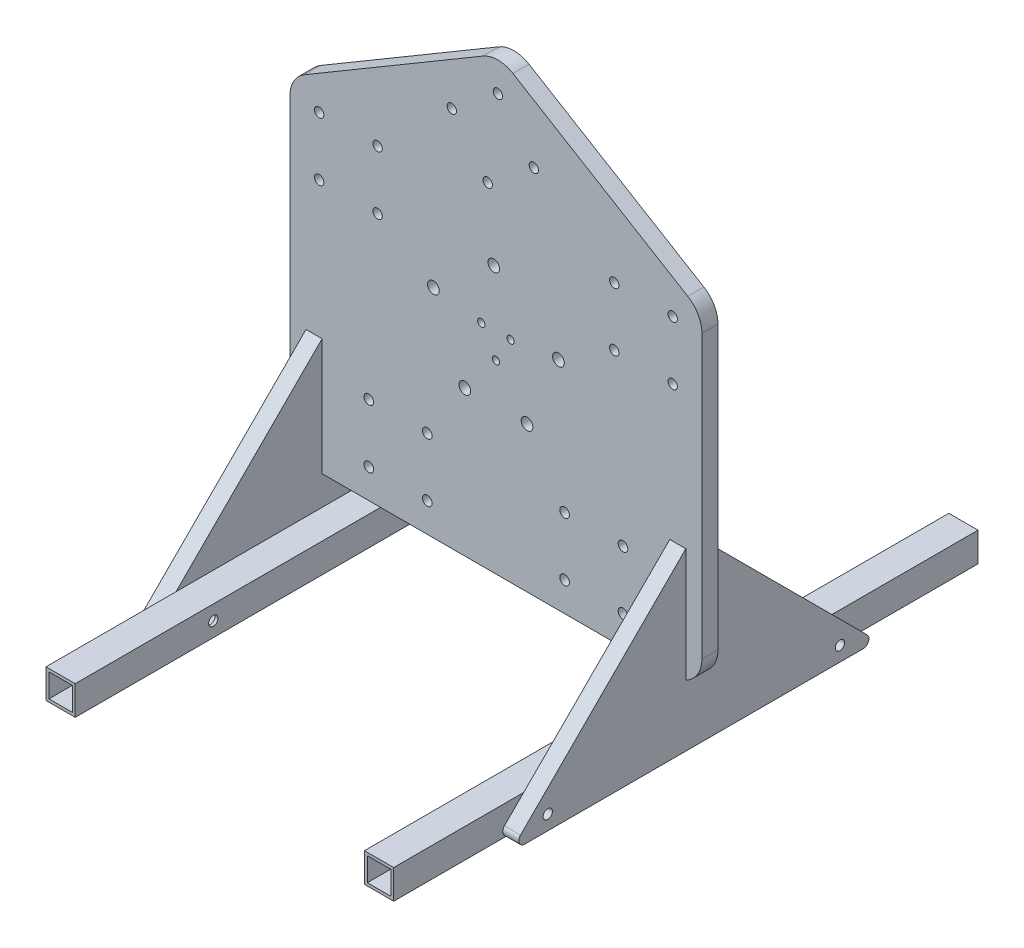
SolidWorks part; units mm, degrees
material "ﾊﾞﾙｻ"
ref_plane "正面" through (0, 0, 0) normal (0, 0, 1) x (1, 0, 0)
ref_plane "平面" through (0, 0, 0) normal (0, 1, 0) x (1, 0, 0)
ref_plane "右側面" through (0, 0, 0) normal (1, 0, 0) x (0, 0, -1)
sketch "ｽｹｯﾁ2" plane through (0, 0, 0) normal (0, 0, 1) x (1, 0, 0)
  line L0 (0, 0) -> (0, -57) construction
  line L5 (-23.5, -27) -> (-43.5, -27) construction
  line L6 (-23.5, -27) -> (-23.5, -47) construction
  line L7 (-23.5, -47) -> (-43.5, -47) construction
  line L8 (-43.5, -27) -> (-43.5, -47) construction
  line L9 (43.5, -27) -> (43.5, -47) construction
  line L10 (23.5, -47) -> (43.5, -47) construction
  line L11 (23.5, -27) -> (23.5, -47) construction
  line L12 (23.5, -27) -> (43.5, -27) construction
  line L13 (-23.5, -27) -> (-6, 0) construction
  line L14 (-40.5, 29.5934) -> (-13.5, 12.0934) construction
  line L15 (40.5, 49.5934) -> (40.5, 29.5934) construction
  line L16 (-60.5, 49.5934) -> (-40.5, 49.5934) construction
  line L17 (-60.5, 49.5934) -> (-60.5, 29.5934) construction
  line L18 (-60.5, 29.5934) -> (-40.5, 29.5934) construction
  line L19 (-40.5, 49.5934) -> (-40.5, 29.5934) construction
  line L20 (60.5, 29.5934) -> (40.5, 29.5934) construction
  line L21 (60.5, 49.5934) -> (60.5, 29.5934) construction
  line L22 (60.5, 49.5934) -> (40.5, 49.5934) construction
  line L23 (40.5, 29.5934) -> (13.5, 12.0934) construction
  line L24 (-2.8043, 57.6463) -> (0, 25.5934) construction
  line L25 (0.6676, 85.7166) -> (12.9669, 69.9455) construction
  line L26 (0.6676, 85.7166) -> (-15.1035, 73.4174) construction
  line L27 (-15.1035, 73.4174) -> (-2.8043, 57.6463) construction
  line L28 (12.9669, 69.9455) -> (-2.8043, 57.6463) construction
  line L29 (23.5, -27) -> (6, 0) construction
  line L30 (-70.5, 49.5934) -> (-70.5, -47)
  line L31 (-60.5, -57) -> (60.5, -57)
  line L32 (70.5, -47) -> (70.5, 49.5934)
  line L33 (65.6685, 58.1542) -> (5.8361, 94.2774)
  line L34 (-4.4175, 94.3272) -> (-65.5851, 58.204)
  line L35 (0, 12.0934) -> (0, 6.3199) construction
  circle A0 centre (-43.5, -47) radius 1.65
  circle A1 centre (-43.5, -27) radius 1.65
  circle A2 centre (-23.5, -27) radius 1.65
  circle A3 centre (-23.5, -47) radius 1.65
  circle A8 centre (23.5, -47) radius 1.65
  circle A9 centre (23.5, -27) radius 1.65
  circle A10 centre (43.5, -27) radius 1.65
  circle A11 centre (43.5, -47) radius 1.65
  circle A12 centre (-60.5, 49.5934) radius 1.6
  circle A13 centre (-60.5, 29.5934) radius 1.6
  circle A14 centre (-40.5, 29.5934) radius 1.6
  circle A15 centre (-40.5, 49.5934) radius 1.6
  circle A16 centre (40.5, 49.5934) radius 1.6
  circle A17 centre (40.5, 29.5934) radius 1.6
  circle A18 centre (60.5, 29.5934) radius 1.6
  circle A19 centre (60.5, 49.5934) radius 1.6
  circle A20 centre (0.6676, 85.7166) radius 1.6
  circle A21 centre (-15.1035, 73.4174) radius 1.6
  circle A22 centre (-2.8043, 57.6463) radius 1.6
  circle A23 centre (12.9669, 69.9455) radius 1.6
  circle A24 centre (0, 12.0934) radius 13.5 construction
  arc A25 (-70.5, -47) -> (-60.5, -57) centre (-60.5, -47) ccw
  arc A26 (60.5, -57) -> (70.5, -47) centre (60.5, -47) ccw
  arc A27 (70.5, 49.5934) -> (65.6685, 58.1542) centre (60.5, 49.5934) ccw
  arc A28 (5.8361, 94.2774) -> (-4.4175, 94.3272) centre (0.6676, 85.7166) ccw
  arc A29 (-70.5, 49.5934) -> (-65.5851, 58.204) centre (-60.5, 49.5934) cw
  circle A30 centre (0, 12.0934) radius 22 construction
  circle A31 centre (-21.3964, 17.2114) radius 2
  circle A32 centre (-0.7426, 34.0809) radius 2
  circle A33 centre (21.3964, 17.2114) radius 2
  circle A34 centre (10.6418, -7.1616) radius 2
  circle A35 centre (-10.6418, -7.1616) radius 2
  circle A36 centre (0, 6.3199) radius 1.25
  circle A37 centre (-5, 14.9801) radius 1.25
  circle A38 centre (5, 14.9801) radius 1.25
  point P83 (0, 12.0934)
  dimension "D5" = 3.3
  dimension "D9" = 3.2
  dimension "D13" = 27
  dimension "D14" = 10
  dimension "D17" = 4
  dimension "D18" = 2.5
  dimension "D1" = 20
  dimension "D2" = 17.5
  dimension "D4" = 20
  dimension "D6" = 6
  dimension "24.5" = 27
  dimension "D7" = 20
  dimension "D8" = 20
  dimension "D10" = 17.5
  dimension "D11" = 27
  dimension "D15" = 185
  dimension "6" = 8.5
  dimension "D20" = 10
  dimension "D12" = 2
  dimension "D19" = 3
extrude "ﾎﾞｽ - 押し出し1" add sketch "ｽｹｯﾁ2" along normal blind 5.5
sketch "ｽｹｯﾁ4" plane through (0, 0, 0) normal (0, 0, -1) x (-1, 0, 0)
  circle A0 centre (0.7426, 34.0809) radius 1.7
  circle A1 centre (-21.3964, 17.2114) radius 1.7
  circle A2 centre (21.3964, 17.2114) radius 1.7
  circle A3 centre (10.6418, -7.1616) radius 1.7
  circle A4 centre (-10.6418, -7.1616) radius 1.7
  circle A6 centre (0, 12.0934) radius 22 construction
  circle A7 centre (0, 12.0934) radius 27
  circle A8 centre (0, 6.3199) radius 1.6
  circle A9 centre (0, 6.3199) radius 1.25 construction
  circle A10 centre (-5, 14.9801) radius 1.6
  circle A11 centre (5, 14.9801) radius 1.6
  dimension "D1" = 3.4
  dimension "D2" = 5
  dimension "D3" = 3.2
extrude "ﾎﾞｽ - 押し出し2" add sketch "ｽｹｯﾁ4" along normal blind 10 separate body
sketch "ｽｹｯﾁ6" plane through (0, 0, 5.5) normal (0, 0, 1) x (1, 0, 0)
  line L0 (0, 0) -> (0, -57) construction
  line L1 (-60.5, -57) -> (60.5, -57) construction
  line L2 (70.5, -47) -> (70.5, 49.5934) construction
  line L3 (59.5, -37) -> (65, -37)
  line L4 (59.5, -37) -> (59.5, -57)
  line L5 (59.5, -57) -> (65, -57)
  line L6 (65, -37) -> (65, -57)
  line L7 (-59.5, -57) -> (-65, -57)
  line L8 (-65, -37) -> (-65, -57)
  line L9 (-59.5, -37) -> (-65, -37)
  line L10 (-59.5, -37) -> (-59.5, -57)
  dimension "D1" = 5.5
  dimension "D2" = 5.5
  dimension "D3" = 20
extrude "ｶｯﾄ - 押し出し1" cut sketch "ｽｹｯﾁ6" against normal through all
sketch "ｽｹｯﾁ7" plane through (65, 0, 0) normal (-1, 0, 0) x (0, 0, 1)
  line L0 (0, -37) -> (5.5, -37)
  line L1 (0, -37) -> (5.5, -37) construction
  line L2 (5.5, -37) -> (5.5, -17)
  line L3 (5.5, -17) -> (65.5, -77)
  line L4 (65.5, -77) -> (-60, -77)
  line L5 (2.75, -77) -> (2.75, -37) construction
  line L6 (5.5, -47) -> (5.5, 49.5934) construction
  line L7 (0, -57) -> (5.5, -57) construction
  line L8 (0, -37) -> (0, -17)
  line L9 (0, -17) -> (-60, -77)
  dimension "D1" = 20
  dimension "D2" = 20
  dimension "D3" = 45
extrude "ﾎﾞｽ - 押し出し3" add sketch "ｽｹｯﾁ7" along normal blind 5.5 separate body
fillet "ﾌｨﾚｯﾄ1" radius 2 2 edges at (62.25, -77, -60) (62.25, -77, 65.5)
mirror "ﾐﾗｰ1" about plane through (0, 0, 0) normal (1, 0, 0) of bodies 104
sketch "ｽｹｯﾁ8" plane through (0, 0, 0) normal (0, 0, 1) x (1, 0, 0)
  line L0 (-58.5, -76) -> (-50.5, -76)
  line L1 (-59.5, -77) -> (-49.5, -77)
  line L2 (-59.5, -77) -> (-59.5, -67)
  line L3 (-59.5, -67) -> (-49.5, -67)
  line L4 (-49.5, -77) -> (-49.5, -67)
  line L5 (-50.5, -76) -> (-50.5, -68)
  line L6 (-58.5, -68) -> (-50.5, -68)
  line L7 (-58.5, -76) -> (-58.5, -68)
  point P9 (0, 0)
  point P10 (0, 0)
  dimension "D1" = 1
  dimension "D2" = 10
  dimension "D3" = 10
extrude "ﾎﾞｽ - 押し出し4" add sketch "ｽｹｯﾁ8" along normal blind 100 and the other way blind 100 separate body
mirror "ﾐﾗｰ2" about plane through (0, 0, 0) normal (1, 0, 0) of bodies 106
sketch "ｽｹｯﾁ9" plane through (65, 0, 0) normal (1, 0, 0) x (0, 0, -1)
  line L0 (-2.75, -55.9303) -> (-2.75, -77) construction
  line L1 (-5.5, -55.9303) -> (0, -55.9303) construction
  line L2 (55.1716, -77) -> (-60.6716, -77) construction
  circle A0 centre (47.25, -72) radius 1.6
  circle A1 centre (-52.75, -72) radius 1.6
  dimension "D1" = 5
  dimension "D3" = 3.2
  dimension "D2" = 100
extrude "ｶｯﾄ - 押し出し2" cut sketch "ｽｹｯﾁ9" against normal through all
